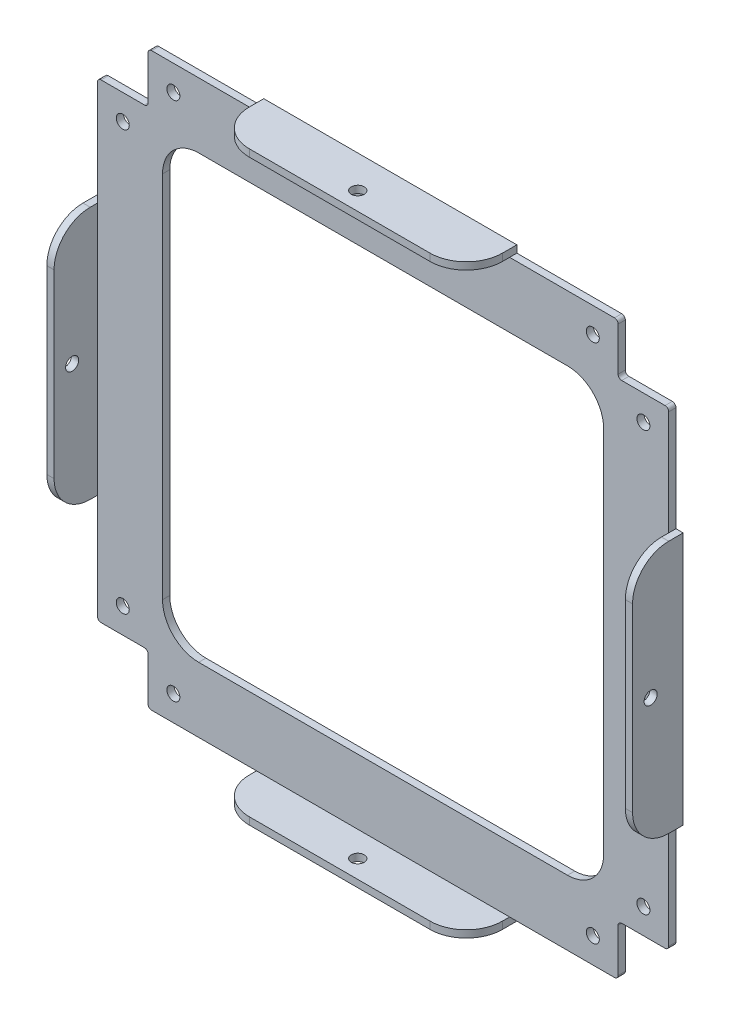
SolidWorks part; units mm, degrees
material "6061 Alloy"
ref_plane "Frontal" through (0, 0, 0) normal (0, 0, 1) x (1, 0, 0)
ref_plane "Superior" through (0, 0, 0) normal (0, 1, 0) x (1, 0, 0)
ref_plane "Direito" through (0, 0, 0) normal (1, 0, 0) x (0, 0, -1)
sketch "Sketch1" plane through (0, 0, 0) normal (0, 0, 1) x (1, 0, 0)
  line L1 (-39.5, -39.5) -> (39.5, -39.5)
  line L2 (-39.5, -39.5) -> (-39.5, 39.5)
  line L3 (-39.5, 39.5) -> (39.5, 39.5)
  line L4 (39.5, -39.5) -> (39.5, 39.5)
  line L5 (-39.5, -39.5) -> (39.5, 39.5) construction
  line L6 (-39.5, 39.5) -> (39.5, -39.5) construction
  point P0 (0, 0)
  dimension "D1" = 79
  dimension "D2" = 79
extrude "Boss-Extrude1" add sketch "Sketch1" along normal mid plane 1
sketch "Sketch2" plane through (0, 0, 0.5) normal (0, 0, 1) x (1, 0, 0)
  line L0 (39.5, 39.5) -> (-39.5, 39.5) construction
  line L1 (-17.5, 40.5) -> (17.5, 40.5)
  line L2 (-17.5, 40.5) -> (-17.5, 39.5)
  line L3 (-17.5, 39.5) -> (17.5, 39.5)
  line L4 (17.5, 40.5) -> (17.5, 39.5)
  line L5 (-39.5, 39.5) -> (-39.5, -39.5) construction
  line L6 (-40.5, 17.5) -> (-39.5, 17.5)
  line L7 (-40.5, 17.5) -> (-40.5, -17.5)
  line L8 (-40.5, -17.5) -> (-39.5, -17.5)
  line L9 (-39.5, 17.5) -> (-39.5, -17.5)
  line L10 (-39.5, -39.5) -> (39.5, -39.5) construction
  line L11 (-17.5, -40.5) -> (17.5, -40.5)
  line L12 (-17.5, -40.5) -> (-17.5, -39.5)
  line L13 (-17.5, -39.5) -> (17.5, -39.5)
  line L14 (17.5, -40.5) -> (17.5, -39.5)
  line L16 (40.5, 17.5) -> (39.5, 17.5)
  line L17 (40.5, 17.5) -> (40.5, -17.5)
  line L18 (40.5, -17.5) -> (39.5, -17.5)
  line L19 (39.5, 17.5) -> (39.5, -17.5)
  line L20 (39.5, -39.5) -> (39.5, 39.5) construction
  dimension "D1" = 1
  dimension "D2" = 35
  dimension "D3" = 22
  dimension "D4" = 1
  dimension "D5" = 35
  dimension "D6" = 22
  dimension "D7" = 1
  dimension "D8" = 35
  dimension "D9" = 22
  dimension "D10" = 1
  dimension "D11" = 35
  dimension "D12" = 22
extrude "Boss-Extrude2" add sketch "Sketch2" along normal blind 6 and the other way blind 1
sketch "Sketch9" plane through (0, 0, 0.5) normal (0, 0, 1) x (1, 0, 0)
  line L1 (-25.5, -30.5) -> (25.5, -30.5)
  line L2 (-30.5, -25.5) -> (-30.5, 25.5)
  line L3 (-25.5, 30.5) -> (25.5, 30.5)
  line L4 (30.5, -25.5) -> (30.5, 25.5)
  line L5 (-25.5, -25.5) -> (25.5, 25.5) construction
  line L6 (-25.5, 25.5) -> (25.5, -25.5) construction
  arc A0 (-25.5, 30.5) -> (-30.5, 25.5) centre (-25.5, 25.5) ccw
  arc A1 (25.5, 30.5) -> (30.5, 25.5) centre (25.5, 25.5) cw
  arc A2 (30.5, -25.5) -> (25.5, -30.5) centre (25.5, -25.5) cw
  arc A3 (-25.5, -30.5) -> (-30.5, -25.5) centre (-25.5, -25.5) cw
  point P0 (0, 0)
  dimension "D1" = 5
  dimension "D2" = 5
  dimension "D3" = 5
  dimension "D4" = 5
  dimension "D5" = 61
  dimension "D6" = 61
extrude "Cut-Extrude1" cut sketch "Sketch9" against normal blind 10
hole_wizard "M1.6 Clearance Hole1" positions "Sketch11" profile "Sketch10" hole size "M1.6" standard "DIN" end condition through all
sketch "Sketch11" plane through (0, 40.5, 0) normal (0, 1, 0) x (1, 0, 0)
  line L0 (17.5, -6.5) -> (-17.5, -6.5) construction
  point P0 (0, -4)
  dimension "D1" = 2.5
sketch "Sketch10" plane through (0, 40.5, 4) normal (1, 0, 0) x (0, 0, 1)
  line L0 (0, 0) -> (0, 81)
  line L1 (0, 81) -> (0.9, 81)
  line L2 (0.9, 81) -> (0.9, 0)
  line L5 (0.9, 0) -> (0, 0)
  line L11 (0, -6.35) -> (0, 107.95) construction
  dimension "Thru Hole Dia." = 1.8
  dimension "Thru Hole Depth" = 81
hole_wizard "M1.6 Clearance Hole2" positions "Sketch14" profile "Sketch13" hole size "M1.6" standard "DIN"
sketch "Sketch14" plane through (-40.5, 0, 0) normal (-1, 0, 0) x (0, 0, 1)
  line L0 (6.5, 17.5) -> (6.5, -17.5) construction
  point P0 (4, 0)
  dimension "D1" = 2.5
sketch "Sketch13" plane through (-40.5, 0, 4) normal (0, 1, 0) x (0, 0, 1)
  line L0 (0, 0) -> (0, 200.5408)
  line L1 (0, 200.5408) -> (0.9, 200)
  line L2 (0.9, 200) -> (0.9, 0)
  line L5 (0.9, 0) -> (0, 0)
  line L10 (0, 200.5408) -> (-0.9, 200) construction
  line L11 (0, -6.35) -> (0, 107.95) construction
  dimension "Hole Dia." = 1.8
  dimension "Hole Depth" = 200
  dimension "Drill Angle" = 118
fillet "Fillet1" radius 5 8 edges at (-40, 17.5, 6.5) (-40, -17.5, 6.5) (-17.5, -40, 6.5) (17.5, -40, 6.5) (40, -17.5, 6.5) (40, 17.5, 6.5) (17.5, 40, 6.5) (-17.5, 40, 6.5)
sketch "Sketch15" plane through (0, 0, 0.5) normal (0, 0, 1) x (1, 0, 0)
  line L0 (-39.5, 39.5) -> (-39.5, 17.5) construction
  line L1 (-39.5, 39.5) -> (-32, 39.5)
  line L2 (-39.5, 39.5) -> (-39.5, 32)
  line L3 (-39, 32.5) -> (-33, 32.5)
  line L4 (-32.5, 39) -> (-32.5, 33)
  line L5 (39.5, 39.5) -> (32, 39.5)
  line L6 (39.5, 39.5) -> (39.5, 32)
  line L7 (39, 32.5) -> (33, 32.5)
  line L8 (32.5, 39) -> (32.5, 33)
  line L9 (-39.5, -39.5) -> (-32, -39.5)
  line L10 (-39.5, -39.5) -> (-39.5, -32)
  line L11 (-39, -32.5) -> (-33, -32.5)
  line L12 (-32.5, -39) -> (-32.5, -33)
  line L13 (39.5, -39.5) -> (32, -39.5)
  line L14 (39.5, -39.5) -> (39.5, -32)
  line L15 (39, -32.5) -> (33, -32.5)
  line L16 (32.5, -39) -> (32.5, -33)
  line L17 (-17.5, 39.5) -> (-39.5, 39.5) construction
  line L18 (39.5, 39.5) -> (17.5, 39.5) construction
  line L19 (39.5, 17.5) -> (39.5, 39.5) construction
  line L20 (39.5, -39.5) -> (39.5, -17.5) construction
  line L21 (17.5, -39.5) -> (39.5, -39.5) construction
  line L22 (-39.5, -17.5) -> (-39.5, -39.5) construction
  line L23 (-39.5, -39.5) -> (-17.5, -39.5) construction
  arc A0 (-32.5, 33) -> (-33, 32.5) centre (-33, 33) cw
  arc A1 (-39, 32.5) -> (-39.5, 32) centre (-39, 32) ccw
  arc A2 (-32.5, 39) -> (-32, 39.5) centre (-32, 39) cw
  arc A3 (32.5, 33) -> (33, 32.5) centre (33, 33) ccw
  arc A4 (32.5, 39) -> (32, 39.5) centre (32, 39) ccw
  arc A5 (39, 32.5) -> (39.5, 32) centre (39, 32) cw
  arc A6 (32.5, -33) -> (33, -32.5) centre (33, -33) cw
  arc A7 (39, -32.5) -> (39.5, -32) centre (39, -32) ccw
  arc A8 (32.5, -39) -> (32, -39.5) centre (32, -39) cw
  arc A9 (-33, -32.5) -> (-32.5, -33) centre (-33, -33) cw
  arc A10 (-39, -32.5) -> (-39.5, -32) centre (-39, -32) cw
  arc A11 (-32.5, -39) -> (-32, -39.5) centre (-32, -39) ccw
  dimension "D9" = 0.5
  dimension "D1" = 0.5
  dimension "D2" = 0.5
  dimension "D3" = 0.5
  dimension "D4" = 0.5
  dimension "D12" = 0.5
  dimension "D5" = 0.5
  dimension "D6" = 0.5
  dimension "D15" = 0.5
  dimension "D7" = 0.5
  dimension "D8" = 0.5
  dimension "D18" = 0.5
  dimension "D10" = 7
  dimension "D11" = 7
  dimension "D13" = 7
  dimension "D14" = 7
  dimension "D16" = 7
  dimension "D17" = 7
  dimension "D19" = 7
  dimension "D20" = 7
extrude "Cut-Extrude2" cut sketch "Sketch15" against normal blind 10
hole_wizard "M1.6 Clearance Hole3" positions "Sketch17" profile "Sketch16" hole size "M1.6" standard "DIN"
sketch "Sketch17" plane through (0, 0, 0.5) normal (0, 0, 1) x (1, 0, 0)
  line L1 (-32.5, 33) -> (-32.5, 39) construction
  line L2 (-39, 32.5) -> (-33, 32.5) construction
  line L3 (-39.5, 32) -> (-39.5, 17.5) construction
  line L4 (-17.5, 39.5) -> (-32, 39.5) construction
  line L5 (32.5, 39) -> (32.5, 33) construction
  line L6 (39.5, 17.5) -> (39.5, 32) construction
  line L7 (39, -32.5) -> (33, -32.5) construction
  line L8 (17.5, -39.5) -> (32, -39.5) construction
  point P0 (-29, 36)
  point P2 (-36, 29)
  point P4 (-36, -29)
  point P6 (-29, -36)
  point P8 (29, -36)
  point P10 (36, -29)
  point P12 (36, 29)
  point P14 (29, 36)
  dimension "D1" = 3.5
  dimension "D2" = 3.5
  dimension "D3" = 3.5
  dimension "D4" = 3.5
  dimension "D5" = 3.5
  dimension "D6" = 3.5
  dimension "D7" = 3.5
  dimension "D8" = 3.5
sketch "Sketch16" plane through (-29, 36, 0.5) normal (1, 0, 0) x (0, -1, 0)
  line L0 (0, 0) -> (0, 200.5408)
  line L1 (0, 200.5408) -> (0.9, 200)
  line L2 (0.9, 200) -> (0.9, 0)
  line L5 (0.9, 0) -> (0, 0)
  line L10 (0, 200.5408) -> (-0.9, 200) construction
  line L11 (0, -6.35) -> (0, 107.95) construction
  dimension "Hole Dia." = 1.8
  dimension "Hole Depth" = 200
  dimension "Drill Angle" = 118
